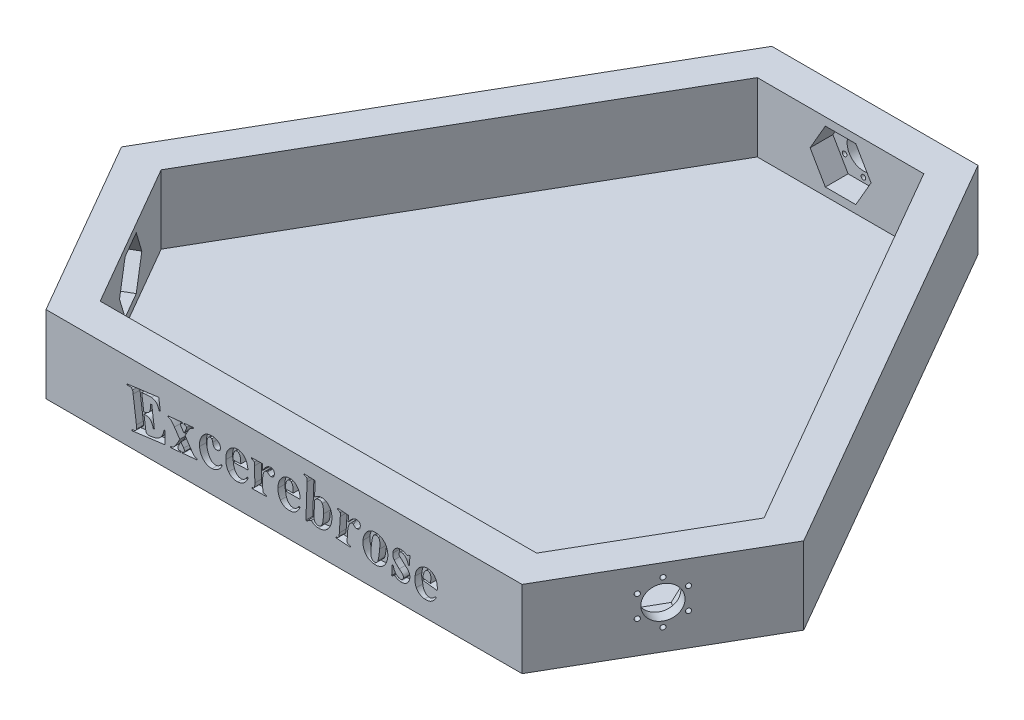
SolidWorks part; units mm, degrees
ref_plane "Front Plane" through (0, 0, 0) normal (0, 0, 1) x (1, 0, 0)
ref_plane "Top Plane" through (0, 0, 0) normal (0, 1, 0) x (1, 0, 0)
ref_plane "Right Plane" through (0, 0, 0) normal (1, 0, 0) x (0, 0, -1)
sketch "Sketch1" plane through (0, 0, 0) normal (0, 1, 0) x (1, 0, 0)
  line L0 (-152.4, 152.4) -> (0, 416.3645)
  line L1 (-152.4, 152.4) -> (152.4, 152.4) construction
  line L2 (-152.4, 152.4) -> (-152.4, -152.4) construction
  line L3 (-152.4, -152.4) -> (152.4, -152.4) construction
  line L4 (152.4, 152.4) -> (152.4, -152.4) construction
  line L5 (-152.4, 152.4) -> (152.4, -152.4) construction
  line L6 (-152.4, -152.4) -> (152.4, 152.4) construction
  line L7 (0, 416.3645) -> (152.4, 152.4)
  line L8 (-152.4, 152.4) -> (24847.6, 43453.6702) construction
  line L9 (152.4, 152.4) -> (-24847.6, 43453.6702) construction
  line L10 (-152.4, -152.4) -> (-328.3764, -152.4)
  line L11 (-328.3764, -152.4) -> (-152.4, 152.4)
  line L12 (152.4, -152.4) -> (328.3764, -152.4)
  line L13 (328.3764, -152.4) -> (152.4, 152.4)
  line L14 (-152.4, -152.4) -> (152.4, -152.4)
  line L15 (-252.1764, -20.4177) -> (-175.9764, -152.4) construction
  line L16 (-76.2, 284.3823) -> (76.2, 284.3823) construction
  line L17 (252.1764, -20.4177) -> (175.9764, -152.4) construction
  point P0 (0, 0)
  dimension "D1" = 304.8
  dimension "D2" = 304.8
  dimension "D3" = 304.8
  dimension "D4" = 304.8
  dimension "D5" = 152.4
  dimension "D6" = 152.4
  dimension "D7" = 152.4
  dimension "D8" = 152.4
  dimension "D9" = 152.4
sketch "Sketch2" plane through (0, 0, 0) normal (0, 1, 0) x (1, 0, 0)
  line L0 (76.2, 284.3823) -> (-76.2, 284.3823)
  line L1 (0, 416.3645) -> (152.4, 152.4) construction
  line L2 (-76.2, 284.3823) -> (-252.1764, -20.4177)
  line L3 (-252.1764, -20.4177) -> (-175.9764, -152.4)
  line L4 (-175.9764, -152.4) -> (175.9764, -152.4)
  line L5 (175.9764, -152.4) -> (252.1764, -20.4177)
  line L6 (252.1764, -20.4177) -> (76.2, 284.3823)
extrude "Boss-Extrude1" add sketch "Sketch2" along normal blind 6.35
sketch "Sketch3" plane through (0, 6.35, 0) normal (0, 1, 0) x (1, 0, 0)
  line L0 (76.2, 284.3823) -> (-76.2, 284.3823)
  line L1 (0, 416.3645) -> (152.4, 152.4) construction
  line L2 (-76.2, 284.3823) -> (-252.1764, -20.4177)
  line L3 (-252.1764, -20.4177) -> (-175.9764, -152.4)
  line L4 (-175.9764, -152.4) -> (175.9764, -152.4)
  line L5 (175.9764, -152.4) -> (252.1764, -20.4177)
  line L6 (252.1764, -20.4177) -> (76.2, 284.3823)
  line L7 (-161.3117, -127) -> (161.3117, -127)
  line L8 (-161.3117, -127) -> (-222.847, -20.4177)
  line L9 (-222.847, -20.4177) -> (-61.5353, 258.9823)
  line L10 (-61.5353, 258.9823) -> (61.5353, 258.9823)
  line L11 (61.5353, 258.9823) -> (222.847, -20.4177)
  line L12 (222.847, -20.4177) -> (161.3117, -127)
  dimension "D1" = 25.4
  dimension "D2" = 25.4
  dimension "D3" = 25.4
  dimension "D4" = 25.4
  dimension "D5" = 25.4
  dimension "D6" = 25.4
extrude "Boss-Extrude2" add sketch "Sketch3" along normal blind 50.8
sketch "Sketch4" plane through (0, 57.15, 0) normal (0, 1, 0) x (1, 0, 0)
  line L0 (-61.5353, 258.9823) -> (-222.847, -20.4177) construction
  line L1 (-76.2, 284.3823) -> (76.2, 284.3823) construction
  line L6 (-61.5353, 258.9823) -> (-61.5353, 182.7823)
  line L8 (-161.3117, -127) -> (161.3117, -127) construction
  line L10 (95.3205, -88.9) -> (-95.3205, -88.9) construction
  line L11 (-222.847, -20.4177) -> (-161.3117, -127) construction
  line L12 (95.3205, -88.9) -> (-95.3205, -88.9)
  line L13 (161.3117, -127) -> (222.847, -20.4177) construction
  line L14 (-61.5353, 182.7823) -> (-156.8558, 17.6823) construction
  line L15 (61.5353, 258.9823) -> (61.5353, 182.7823)
  line L16 (222.847, -20.4177) -> (61.5353, 258.9823) construction
  line L17 (-61.5353, 182.7823) -> (-156.8558, 17.6823)
  line L18 (156.8558, 17.6823) -> (61.5353, 182.7823)
  line L19 (-61.5353, 258.9823) -> (-61.5353, 284.3823)
  line L20 (-61.5353, 284.3823) -> (61.5353, 284.3823)
  line L21 (61.5353, 284.3823) -> (61.5353, 258.9823)
  line L22 (-222.847, -20.4177) -> (-156.8558, 17.6823)
  line L23 (-161.3117, -127) -> (-95.3205, -88.9)
  line L24 (161.3117, -127) -> (95.3205, -88.9)
  line L25 (222.847, -20.4177) -> (156.8558, 17.6823)
  line L26 (161.3117, -127) -> (222.847, -20.4177) construction
  line L28 (61.5353, 182.7823) -> (156.8558, 17.6823) construction
  line L29 (-222.847, -20.4177) -> (-244.844, -33.1177)
  line L30 (-252.1764, -20.4177) -> (-175.9764, -152.4) construction
  line L31 (-161.3117, -127) -> (-183.3087, -139.7)
  line L32 (-183.3087, -139.7) -> (-244.844, -33.1177)
  line L33 (161.3117, -127) -> (183.3087, -139.7)
  line L34 (252.1764, -20.4177) -> (175.9764, -152.4) construction
  line L35 (222.847, -20.4177) -> (244.844, -33.1177)
  line L36 (244.844, -33.1177) -> (183.3087, -139.7)
  dimension "D1" = 38.1
  dimension "D2" = 38.1
  dimension "D3" = 38.1
  dimension "D4" = 90
  dimension "D5" = 90
  dimension "D6" = 90
  dimension "D7" = 90
extrude "Boss-Extrude3" add sketch "Sketch4" along normal blind 6.35 contours L12 L23 L31 L32 L29 L22 L17 L6 L19 L20 L21 L15 L18 L25 L35 L36 L33 L24
sketch "Sketch8" plane through (0, 0, -284.3823) normal (0, 0, -1) x (-1, 0, 0)
  line L0 (-61.5353, 57.15) -> (-61.5353, 0) construction
  line L1 (-76.2, 0) -> (76.2, 0) construction
  line L2 (-61.5353, 0) -> (61.5353, 63.5) construction
  line L4 (0, 15.75) -> (13.8564, 23.75) construction
  line L5 (13.8564, 23.75) -> (13.8564, 39.75) construction
  line L6 (13.8564, 39.75) -> (0, 47.75) construction
  line L7 (0, 47.75) -> (-13.8564, 39.75) construction
  line L8 (-13.8564, 39.75) -> (-13.8564, 23.75) construction
  line L9 (-13.8564, 23.75) -> (0, 15.75) construction
  circle A0 centre (0, 31.75) radius 16 construction
  circle A1 centre (0, 31.75) radius 16 construction
  circle A2 centre (-13.8564, 39.75) radius 1.7
  circle A3 centre (0, 47.75) radius 1.7
  circle A4 centre (13.8564, 39.75) radius 1.7
  circle A5 centre (13.8564, 23.75) radius 1.7
  circle A6 centre (0, 15.75) radius 1.7 [skipped]
  circle A7 centre (-13.8564, 23.75) radius 1.7
  circle A8 centre (0, 31.75) radius 12
  circle A9 centre (0, 47.75) radius 1.7 [skipped]
  circle A10 centre (13.8564, 39.75) radius 1.7 [skipped]
  circle A11 centre (13.8564, 23.75) radius 1.7 [skipped]
  circle A12 centre (0, 15.75) radius 1.7
  circle A13 centre (-13.8564, 23.75) radius 1.7 [skipped]
  point P30 (0, 31.75)
  point P41 (0, 31.75)
  dimension "D1" = 32
  dimension "D2" = 3.4
  dimension "D4" = 24
  dimension "D3" = 6
  dimension "D5" = 6
extrude "Cut-Extrude1" cut sketch "Sketch8" against normal up to next
sketch "Sketch9" plane through (0, 0, -258.9823) normal (0, 0, 1) x (1, 0, 0)
  line L1 (11.2589, 51.251) -> (-11.2589, 51.251)
  line L2 (-11.2589, 51.251) -> (-22.5178, 31.75)
  line L3 (-22.5178, 31.75) -> (-11.2589, 12.249)
  line L4 (-11.2589, 12.249) -> (11.2589, 12.249)
  line L5 (11.2589, 12.249) -> (22.5178, 31.75)
  line L6 (22.5178, 31.75) -> (11.2589, 51.251)
  circle A1 centre (0, 31.75) radius 19.501 construction
  dimension "D1" = 39.0021
extrude "Cut-Extrude2" cut sketch "Sketch9" against normal blind 16.86
sketch "Sketch11" plane through (0, 63.5, 0) normal (0, 1, 0) x (1, 0, 0)
  line L0 (0, 284.3823) -> (0, -88.9)
  line L1 (-61.5353, 284.3823) -> (61.5353, 284.3823) construction
  line L2 (95.3205, -88.9) -> (-95.3205, -88.9) construction
  line L3 (0, -88.9) -> (-214.0764, -86.4089)
  line L4 (-183.3087, -139.7) -> (-244.844, -33.1177) construction
  line L5 (-214.0764, -86.4089) -> (109.1956, 100.2323)
  line L6 (156.8558, 17.6823) -> (61.5353, 182.7823) construction
  line L7 (109.1956, 100.2323) -> (214.0764, -86.4089)
  line L8 (244.844, -33.1177) -> (183.3087, -139.7) construction
  line L9 (214.0764, -86.4089) -> (-109.1956, 100.2323)
  line L10 (-61.5353, 182.7823) -> (-156.8558, 17.6823) construction
  point P18 (0, 37.1882)
sketch "Sketch12" plane through (0, 0, 0) normal (1, 0, 0) x (0, 0, -1)
  line L0 (37.1882, 63.5) -> (37.1882, -49936.5) construction
pattern_circular "CirPattern1" count 3 over 360 about axis through (0, 63.5, -37.1882) along (0, -1, 0) of "Cut-Extrude2", "Cut-Extrude1"
sketch "Sketch13" plane through (0, 63.5, 0) normal (0, 1, 0) x (1, 0, 0)
  line L1 (-390.8937, 293.283) -> (378.216, 293.283)
  line L2 (-390.8937, 293.283) -> (-390.8937, -172.7709)
  line L3 (-390.8937, -172.7709) -> (378.216, -172.7709)
  line L4 (378.216, 293.283) -> (378.216, -172.7709)
  line L5 (-390.8937, 293.283) -> (378.216, -172.7709) construction
  line L6 (-390.8937, -172.7709) -> (378.216, 293.283) construction
  point P0 (-6.3388, 60.256)
ref_axis "Axis1" through (0, 63.5, -37.1882) along (0, -1, 0)
sketch "Sketch14" plane through (0, 63.5, 0) normal (0, 1, 0) x (1, 0, 0)
  line L1 (-384.2492, 326.6729) -> (384.2492, 326.6729)
  line L2 (-384.2492, 326.6729) -> (-384.2492, -252.2965)
  line L3 (-384.2492, -252.2965) -> (384.2492, -252.2965)
  line L4 (384.2492, 326.6729) -> (384.2492, -252.2965)
  line L5 (-384.2492, 326.6729) -> (384.2492, -252.2965) construction
  line L6 (-384.2492, -252.2965) -> (384.2492, 326.6729) construction
  point P0 (0, 37.1882)
extrude "Cut-Extrude3" cut sketch "Sketch14" against normal blind 6.35
sketch "Sketch15" plane through (0, 0, 152.4) normal (0, 0, 1) x (1, 0, 0)
  line L0 (-175.9764, 0) -> (-175.9764, 57.15) construction
  line L1 (-175.9764, 0) -> (-175.9764, 19.05) construction
  line L2 (-175.9764, 19.05) -> (175.9764, 19.05) construction
  line L3 (175.9764, 57.15) -> (175.9764, 0) construction
  arc A0 (-175.9764, 0) -> (175.9764, 0) centre (0, -803.275) cw construction
  text T0 "Excerebrose" font "Times New Roman" height in points 120
  dimension "D1" = 19.05
extrude "Cut-Extrude4" cut sketch "Sketch15" against normal blind 5.08
equation "\"l\"= 12"
equation "\"D1@Sketch1\"=\"l\""
equation "\"w\"= 12"
equation "\"D2@Sketch1\"=\"w\""
equation "\"D3@Sketch1\"=\"w\""
equation "\"D4@Sketch1\"=\"w\""
equation "\"d\"=6"
equation "\"D5@Sketch1\"=\"d\""
equation "\"D6@Sketch1\"=\"d\""
equation "\"D7@Sketch1\"=\"d\""
equation "\"D8@Sketch1\"=\"d\""
equation "\"D9@Sketch1\"=\"d\""
equation "\"barW\"=1"
equation "\"D4@Sketch3\"=\"barW\""
equation "\"D3@Sketch3\"=\"barW\""
equation "\"D2@Sketch3\"=\"barW\""
equation "\"D1@Sketch3\"=\"barW\""
equation "\"D6@Sketch3\"=\"barW\""
equation "\"D5@Sketch3\"=\"barW\""
equation "\"barH\"=2"
equation "\"D1@Boss-Extrude2\"=\"barH\""
equation "\"batW\"=1.5"
equation "\"D1@Sketch4\"=\"batW\""
equation "\"D2@Sketch4\"=\"batW\""
equation "\"D3@Sketch4\"=\"batW\""
